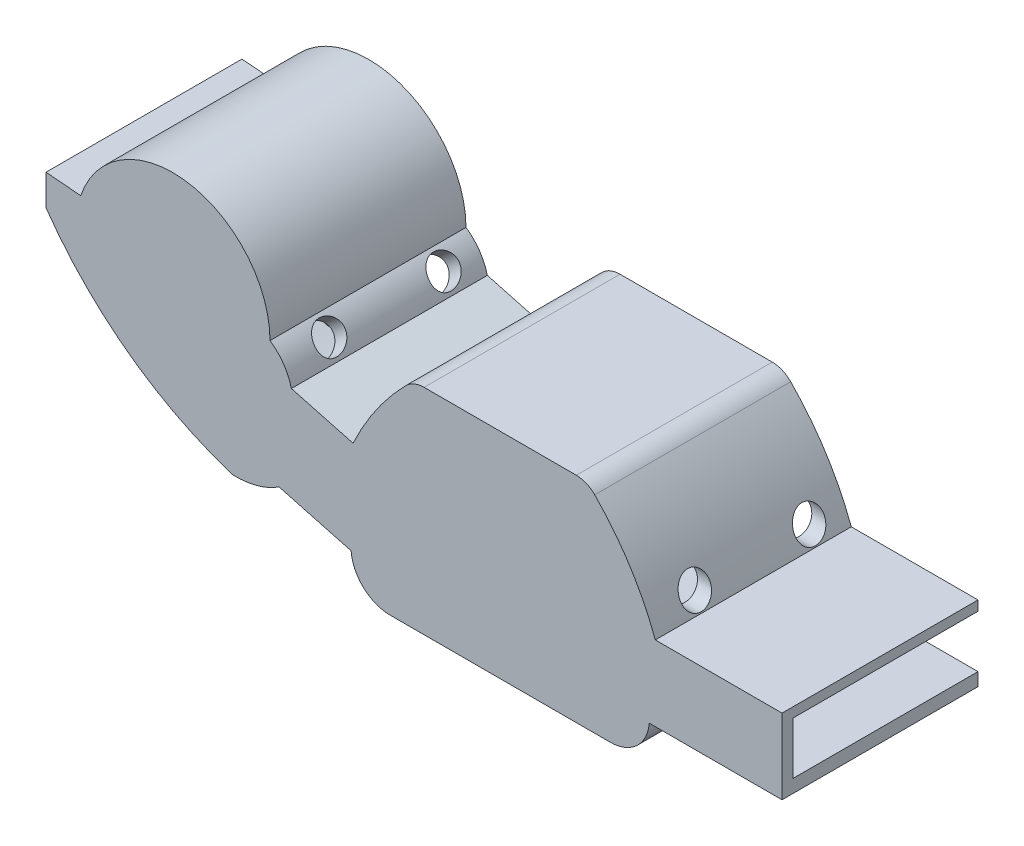
SolidWorks part; units mm, degrees
ref_plane "Front Plane" through (0, 0, 0) normal (0, 0, 1) x (1, 0, 0)
ref_plane "Top Plane" through (0, 0, 0) normal (0, 1, 0) x (1, 0, 0)
ref_plane "Right Plane" through (0, 0, 0) normal (1, 0, 0) x (0, 0, -1)
sketch "Sketch1" plane through (0, 0, 0) normal (0, 0, 1) x (1, 0, 0)
  line L23 (-11.1807, 10.652) -> (-11.4807, 9.152)
  line L24 (-11.4807, 9.152) -> (-11.7807, 10.652)
  line L25 (-11.7807, 10.652) -> (-12.4807, 10.652)
  line L36 (-12.4807, 10.652) -> (-12.7807, 9.152)
  line L40 (-12.7807, 9.152) -> (-13.0807, 10.652)
  line L41 (-13.0807, 10.652) -> (-13.7547, 10.652)
  line L47 (-13.7547, 10.652) -> (-14.0547, 9.152)
  line L48 (-14.0547, 9.152) -> (-14.3547, 10.652)
  line L49 (-14.3547, 10.652) -> (-15.0547, 10.652)
  line L50 (-15.0547, 10.652) -> (-15.3547, 9.152)
  line L51 (-15.3547, 9.152) -> (-15.6547, 10.652)
  line L52 (-15.6547, 10.652) -> (-16.3547, 10.652)
  line L53 (-16.3547, 10.652) -> (-16.6547, 9.152)
  line L54 (-16.6547, 9.152) -> (-16.9547, 10.652)
  line L55 (-16.9547, 10.652) -> (-17.6547, 10.652)
  line L80 (-17.6547, 10.652) -> (-17.9547, 9.152)
  line L171 (8.2817, 1.895) -> (-3.6348, 1.895)
  line L172 (-10.5067, 10.652) -> (-11.1807, 10.652)
  line L173 (-9.9067, 10.652) -> (-9.3532, 10.652)
  line L175 (-46.0443, 15.2577) -> (-46.3443, 16.3976)
  line L176 (-9.9067, 10.652) -> (-10.2067, 9.152)
  line L177 (-10.2067, 9.152) -> (-10.5067, 10.652)
  line L178 (-49.6428, 15.7937) -> (-49.9428, 14.4937)
  line L179 (-3.7183, -2.905) -> (8.2817, -2.905)
  line L180 (-2.7142, -4.105) -> (9.4817, -4.105)
  line L183 (9.4817, 2.795) -> (9.4817, -4.105)
  line L184 (8.2817, 1.895) -> (8.2817, -2.905)
  line L185 (-2.1578, 2.795) -> (9.4817, 2.795)
  line L186 (-54.0874, 6.0654) -> (-57.3849, 10.0091)
  line L188 (-43.4443, 14.6312) -> (-43.7443, 15.8853)
  line L189 (-34.4134, -2.9319) -> (-30.1025, -4.0888)
  line L190 (-58.1264, 9.1857) -> (-58.1264, 12.0173)
  line L195 (-57.3849, 10.0091) -> (-57.3849, 10.7452)
  line L197 (-40.8443, 12.4754) -> (-41.1443, 14.2875)
  line L198 (-47.0455, 16.3874) -> (-47.3455, 15.1968)
  line L199 (-36.8194, 5.1686) -> (-29.0928, 3.095)
  line L200 (-23.1547, 9.152) -> (-23.4579, 10.6577)
  line L202 (-47.3455, 15.1968) -> (-47.6455, 16.3297)
  line L204 (-51.2409, 13.6138) -> (-51.5409, 14.6859)
  line L205 (-55.3415, 9.1857) -> (-56.9992, 10.3046)
  line L206 (-49.9428, 14.4937) -> (-50.2428, 15.5168)
  line L208 (-40.5443, 13.6754) -> (-40.8443, 12.4754)
  line L209 (-57.3849, 10.7452) -> (-56.9992, 10.3046)
  line L210 (-42.1443, 13.7602) -> (-42.4443, 15.2573)
  line L211 (-44.4443, 16.1129) -> (-44.7443, 15.0629)
  line L213 (-39.2443, 11.6575) -> (-39.5443, 9.6575)
  line L214 (-44.7443, 15.0629) -> (-45.0443, 16.2535)
  line L215 (-52.2425, 14.0661) -> (-52.5425, 12.1661)
  line L218 (-45.7443, 16.3577) -> (-46.0443, 15.2577)
  line L219 (-50.9409, 15.1138) -> (-51.2409, 13.6138)
  line L220 (-37.9614, -0.7373) -> (-29.1114, -3.1123)
  line L222 (-39.5443, 9.6575) -> (-39.8443, 12.7549)
  line L223 (-41.8443, 14.8602) -> (-42.1443, 13.7602)
  line L224 (-52.5425, 12.1661) -> (-52.8425, 13.3998)
  line L226 (-58.1264, 12.0173) -> (-54.9379, 11.7458)
  line L229 (-43.1443, 15.6312) -> (-43.4443, 14.6312)
  line L230 (-48.3433, 16.2047) -> (-48.6433, 14.9476)
  line L232 (-29.9206, 4.5597) -> (-35.5859, 6.08)
  line L236 (-48.6433, 14.9476) -> (-48.9433, 16.045)
  line L237 (-34.4134, -2.9319) -> (-36.7107, -2.3154)
  line L238 (-19.2547, 9.152) -> (-19.5547, 10.652)
  line L239 (-17.9547, 9.152) -> (-18.2547, 10.652)
  line L240 (-20.2547, 10.652) -> (-20.5547, 9.152)
  line L241 (-18.2547, 10.652) -> (-18.9547, 10.652)
  line L242 (-18.9547, 10.652) -> (-19.2547, 9.152)
  line L243 (-20.8547, 10.652) -> (-21.5547, 10.652)
  line L244 (-20.5547, 9.152) -> (-20.8547, 10.652)
  line L245 (-19.5547, 10.652) -> (-20.2547, 10.652)
  line L246 (-21.5547, 10.652) -> (-21.8547, 9.152)
  line L247 (-22.1547, 10.652) -> (-22.8547, 10.652)
  line L248 (-22.8547, 10.652) -> (-23.1547, 9.152)
  line L249 (-21.8547, 9.152) -> (-22.1547, 10.652)
  line L253 (-23.3968, 12.2681) -> (-9.4143, 12.2681)
  line L254 (-26.0691, -6.2141) -> (-6.7463, -6.2141)
  line L255 (-6.3025, -7.4141) -> (-26.513, -7.4141)
  arc A66 (-2.7142, -4.105) -> (-6.3025, -7.4141) centre (-6.3025, -3.8141) cw
  arc A67 (-3.7183, -2.905) -> (-6.7463, -6.2141) centre (-6.7023, -3.2144) cw
  arc A69 (-7.343, 8.6822) -> (-9.3532, 10.652) centre (-10.3911, 7.5822) ccw
  arc A70 (-7.343, 8.6822) -> (-3.6348, 1.895) centre (-11.6135, 1.9424) cw
  arc A71 (-2.1578, 2.795) -> (-7.7202, 11.551) centre (-25.381, -5.8132) ccw
  arc A72 (-9.4143, 12.2681) -> (-7.7202, 11.551) centre (-9.4143, 9.9085) cw
  arc A73 (-38.5443, 8.0298) -> (-39.2443, 11.6575) centre (-46.5774, 8.3611) ccw
  arc A75 (-23.3968, 12.2681) -> (-25.0909, 11.551) centre (-23.3968, 9.9085) ccw
  arc A76 (-51.5409, 14.6859) -> (-52.2425, 14.0661) centre (-46.5774, 8.3611) ccw
  arc A77 (-29.1114, -3.1123) -> (-26.0691, -6.2141) centre (-26.1131, -3.2144) ccw
  arc A78 (-58.1264, 9.1857) -> (-41.0218, -3.467) centre (-30.718, 28.3501) ccw
  arc A79 (-42.4443, 15.2573) -> (-43.1443, 15.6312) centre (-46.5774, 8.3611) ccw
  arc A80 (-46.3443, 16.3976) -> (-47.0455, 16.3874) centre (-46.5774, 8.3611) ccw
  arc A81 (-47.6455, 16.3297) -> (-48.3433, 16.2047) centre (-46.5774, 8.3611) ccw
  arc A84 (-54.0874, 6.0654) -> (-41.4637, -2.3822) centre (-33.3409, 23.4122) ccw
  arc A87 (-30.1025, -4.0888) -> (-26.513, -7.4141) centre (-26.513, -3.8141) ccw
  arc A89 (-43.7443, 15.8853) -> (-44.4443, 16.1129) centre (-46.5774, 8.3611) ccw
  arc A90 (-48.9433, 16.045) -> (-49.6428, 15.7937) centre (-46.5774, 8.3611) ccw
  arc A91 (-54.9379, 11.7458) -> (-37.5473, 8.9146) centre (-46.4786, 8.8809) cw
  arc A92 (-39.8443, 12.7549) -> (-40.5443, 13.6754) centre (-46.5774, 8.3611) ccw
  arc A93 (-41.4637, -2.3822) -> (-37.9614, -0.7373) centre (-40.6872, 0.5156) ccw
  arc A94 (-50.2428, 15.5168) -> (-50.9409, 15.1138) centre (-46.5774, 8.3611) ccw
  arc A96 (-24.9838, 9.9746) -> (-25.4681, 8.6822) centre (-23.5017, 8.6822) ccw
  arc A98 (-52.8425, 13.3998) -> (-54.5321, 9.5285) centre (-46.5774, 8.3611) ccw
  arc A100 (-36.8194, 5.1686) -> (-38.5443, 8.0298) centre (-40.8332, 4.6994) ccw
  arc A101 (-23.4579, 10.6577) -> (-24.9838, 9.9746) centre (-23.4814, 8.6645) ccw
  arc A102 (-45.0443, 16.2535) -> (-45.7443, 16.3577) centre (-46.5774, 8.3611) ccw
  arc A104 (-29.9206, 4.5597) -> (-25.0909, 11.551) centre (-7.4301, -5.8132) cw
  arc A106 (-41.1443, 14.2875) -> (-41.8443, 14.8602) centre (-46.5774, 8.3611) ccw
  arc A107 (-36.7107, -2.3154) -> (-41.0218, -3.467) centre (-40.6418, 3.756) cw
  arc A109 (-35.5859, 6.08) -> (-37.5473, 8.9146) centre (-40.294, 4.9182) ccw
  arc A110 (-25.4681, 8.6822) -> (-29.0928, 3.095) centre (-21.1976, 1.9424) ccw
  arc A111 (-54.5321, 9.5285) -> (-55.3415, 9.1857) centre (-48.0159, -6.9857) ccw
  dimension "D14" = 12
  dimension "D18" = 4.8
  dimension "D19" = 6.9
  dimension "D20" = 11.9164
extrude "Walls" add sketch "Sketch1" along normal blind 16 contours L242 region at (-4.3511, -5.93, 0)
sketch "Sketch2" plane through (0, 0, 0) normal (0, 0, -1) x (-1, 0, 0)
  line L10 (35.5859, 6.08) -> (29.9206, 4.5597)
  line L12 (35.5859, 6.08) -> (29.9206, 4.5597)
  line L15 (2.1578, 2.795) -> (-9.4817, 2.795)
  line L17 (2.1578, 2.795) -> (-9.4817, 2.795)
  line L18 (-9.4817, 2.795) -> (-9.4817, -4.105)
  line L37 (-9.4817, 2.795) -> (-9.4817, -4.105)
  line L38 (-9.4817, -4.105) -> (2.7142, -4.105)
  line L39 (-9.4817, -4.105) -> (2.7142, -4.105)
  line L40 (23.3968, 12.2681) -> (9.4143, 12.2681)
  line L42 (23.3968, 12.2681) -> (9.4143, 12.2681)
  line L44 (6.3025, -7.4141) -> (26.513, -7.4141)
  line L47 (6.3025, -7.4141) -> (26.513, -7.4141)
  line L53 (30.1025, -4.0888) -> (36.7107, -2.3154)
  line L54 (30.1025, -4.0888) -> (36.7107, -2.3154)
  line L55 (58.1264, 9.1857) -> (58.1264, 12.0173)
  line L56 (58.1264, 9.1857) -> (58.1264, 12.0173)
  line L57 (58.1264, 12.0173) -> (54.9379, 11.7458)
  line L58 (58.1264, 12.0173) -> (54.9379, 11.7458)
  arc A16 (9.4143, 12.2681) -> (7.7202, 11.551) centre (9.4143, 9.9085) ccw
  arc A17 (9.4143, 12.2681) -> (7.7202, 11.551) centre (9.4143, 9.9085) ccw
  arc A25 (7.7202, 11.551) -> (2.1578, 2.795) centre (25.381, -5.8132) ccw
  arc A26 (7.7202, 11.551) -> (2.1578, 2.795) centre (25.381, -5.8132) ccw
  arc A27 (2.7142, -4.105) -> (6.3025, -7.4141) centre (6.3025, -3.8141) ccw
  arc A28 (2.7142, -4.105) -> (6.3025, -7.4141) centre (6.3025, -3.8141) ccw
  arc A30 (29.9206, 4.5597) -> (25.0909, 11.551) centre (7.4301, -5.8132) ccw
  arc A31 (29.9206, 4.5597) -> (25.0909, 11.551) centre (7.4301, -5.8132) ccw
  arc A32 (25.0909, 11.551) -> (23.3968, 12.2681) centre (23.3968, 9.9085) ccw
  arc A33 (25.0909, 11.551) -> (23.3968, 12.2681) centre (23.3968, 9.9085) ccw
  arc A34 (26.513, -7.4141) -> (30.1025, -4.0888) centre (26.513, -3.8141) ccw
  arc A35 (26.513, -7.4141) -> (30.1025, -4.0888) centre (26.513, -3.8141) ccw
  arc A58 (36.7107, -2.3154) -> (41.0218, -3.467) centre (40.6418, 3.756) ccw
  arc A59 (36.7107, -2.3154) -> (41.0218, -3.467) centre (40.6418, 3.756) ccw
  arc A60 (41.0218, -3.467) -> (58.1264, 9.1857) centre (30.718, 28.3501) ccw
  arc A61 (41.0218, -3.467) -> (58.1264, 9.1857) centre (30.718, 28.3501) ccw
  arc A62 (54.9379, 11.7458) -> (37.5473, 8.9146) centre (46.4786, 8.8809) ccw
  arc A63 (54.9379, 11.7458) -> (37.5473, 8.9146) centre (46.4786, 8.8809) ccw
  arc A64 (37.5473, 8.9146) -> (35.5859, 6.08) centre (40.294, 4.9182) ccw
  arc A65 (37.5473, 8.9146) -> (35.5859, 6.08) centre (40.294, 4.9182) ccw
  dimension "D1" = 0
extrude "Base" add sketch "Sketch2" along normal blind 1
sketch "Sketch3" [suppressed] plane through (0, 0, 0) normal (0, 0, 1) x (1, 0, 0)
  line L4 (-65.1711, 5.3832) -> (-63.3958, 4.9067) construction
  line L5 (-84.8697, 19.5134) -> (-85.1843, 17.3997) construction
  line L6 (-51.77, 3.095) -> (-68.5693, 3.095) construction
  line L7 (-68.5693, 6.2951) -> (-68.5693, 3.095) construction
  line L8 (-51.77, 3.095) -> (-54.6697, 3.095) construction
  line L9 (-68.5693, 6.2951) -> (-65.1711, 5.3832) construction
  line L10 (-56.4697, 3.095) -> (-54.6697, 3.095) construction
  line L11 (-80.595, 9.5224) -> (-82.2789, 9.9743)
  line L12 (-80.595, 9.5224) -> (-76.2959, 8.3687) construction
  line L13 (-91.8537, 12.2226) -> (-90.116, 11.8146)
  line L14 (-82.2789, 9.9743) -> (-90.116, 11.8146) construction
  line L15 (-40.77, 3.095) -> (-37.27, 3.095) construction
  line L16 (-3.6422, 1.595) -> (-7.1422, 1.595) construction
  line L17 (-40.77, 3.095) -> (-3.7183, 3.095) construction
  line L18 (-22.2442, 8.652) -> (-22.2442, 3.095) construction
  line L19 (-22.8547, 10.652) -> (-22.1547, 10.652) construction
  line L20 (-22.2442, 10.652) -> (-22.2442, 8.652) construction
  line L21 (-37.27, 3.095) -> (-34.1769, 3.095) construction
  line L22 (-11.7175, 3.095) -> (-7.1422, 1.595) construction
  arc A1 (-82.2789, 9.9743) -> (-90.116, 11.8146) centre (-86.0365, 11.58) ccw
  arc A2 (-91.8537, 12.2226) -> (-80.595, 9.5224) centre (-86.0443, 11.6231) cw
  arc A3 (-54.6697, 3.095) -> (-65.1711, 5.3832) centre (-60.1697, 3.095) ccw construction
  arc A4 (-84.5208, 19.4536) -> (-85.2208, 19.5578) centre (-86.0539, 11.5612) ccw construction
  arc A5 (-56.4697, 3.095) -> (-63.3958, 4.9067) centre (-60.1697, 3.095) ccw construction
  arc A6 (-3.6422, 1.595) -> (-7.343, 8.6822) centre (-11.6135, 1.9424) ccw construction
  arc A7 (-7.1422, 1.595) -> (-37.27, 3.095) centre (-22.9472, -12.5401) ccw construction
  arc A8 (-11.7175, 3.095) -> (-34.1769, 3.095) centre (-22.9472, -12.5401) ccw construction
  dimension "D1" = 11
  dimension "D2" = 2.137
  dimension "D3" = 7.4
  dimension "D8" = 38.5
  dimension "D4" = 3.5184
  dimension "D5" = 3.5
  dimension "D6" = 3.5
  dimension "D7" = 2
sketch "Sketch4" [suppressed] plane through (0, 0, 16) normal (0, 0, 1) x (1, 0, 0)
  line L7 (-69.5947, 0.3005) -> (-71.4824, -0.3779)
  line L10 (-71.4824, -0.3779) -> (-76.1872, 0.8847)
  line L11 (-76.1872, 0.8847) -> (-77.6773, 2.0433)
  line L12 (-40.77, 3.095) -> (-41.1043, 4.1128)
  line L13 (-41.1043, 4.1128) -> (-49.5364, 4.1128)
  line L16 (-67.7226, 6.3478) -> (-68.9499, 7.6397)
  line L17 (-68.9499, 7.6397) -> (-75.0624, 9.2801)
  line L18 (-75.0624, 9.2801) -> (-76.3177, 7.7352)
  line L19 (-49.5364, 4.1128) -> (-51.77, 3.095)
  line L20 (-40.7743, -2.905) -> (-41.0926, -4.1129)
  line L21 (-41.0926, -4.1129) -> (-49.3636, -4.1129)
  line L22 (-49.3636, -4.1129) -> (-51.8007, -2.905)
  arc A0 (-67.7226, 6.3478) -> (-76.3177, 7.7352) centre (-69.7742, 20.955) cw
  arc A1 (-69.5947, 0.3005) -> (-77.6773, 2.0433) centre (-76.3689, -11.5028) ccw
  arc A2 (-40.7743, -2.905) -> (-51.8007, -2.905) centre (-46.2875, -28.5004) ccw
  arc A3 (-40.77, 3.095) -> (-51.77, 3.095) centre (-46.27, 28.5687) cw
extrude "Joint Width" [suppressed] add sketch "Sketch4" against normal blind 16
ref_plane "SideAnchorPlane" through (0, 0, 2.5) normal (0, 0, 1) x (1, 0, 0)
ref_plane "CentralAnchorPlane" through (0, 0, 13) normal (0, 0, 1) x (1, 0, 0)
sketch "Sketch5" [suppressed] plane through (0, 0, 3) normal (0, 0, 1) x (1, 0, 0)
  line L0 (-76.2959, 8.3687) -> (-68.5693, 6.2951) construction
  line L1 (-76.592, 9.4835) -> (-67.8744, 7.144) construction
  line L2 (-77.4258, 10.7304) -> (-66.9487, 7.9187) construction
  line L3 (-76.592, 9.4835) -> (-88.7757, 4.7797)
  line L4 (-77.4258, 10.7304) -> (-90.1205, 5.8293)
  line L5 (-78.0158, 11.7317) -> (-91.096, 6.6818)
  line L6 (-76.2959, 8.3687) -> (-87.6359, 3.9906)
  line L7 (-78.0158, 11.7317) -> (-77.4258, 10.7304)
  line L9 (-76.592, 9.4835) -> (-76.0479, 8.9395)
  line L10 (-76.0479, 8.9395) -> (-76.2959, 8.3687)
  line L11 (-91.096, 6.6818) -> (-91.096, 6.0024)
  line L12 (-91.096, 6.0024) -> (-90.1205, 5.8293)
  line L13 (-88.7757, 4.7797) -> (-88.5883, 3.9906)
  line L14 (-88.5883, 3.9906) -> (-87.6359, 3.9906)
  arc A0 (-76.2959, 8.3687) -> (-78.0208, 11.2299) centre (-80.3097, 7.8995) ccw construction
  arc A1 (-65.3947, 8.6822) -> (-68.5693, 6.2951) centre (-63.493, 2.8486) ccw construction
  arc A2 (-76.2959, 8.3687) -> (-78.0208, 11.2299) centre (-80.3097, 7.8995) ccw construction
  arc A4 (-93.5639, 9.2655) -> (-80.9402, 0.8179) centre (-72.8174, 26.6123) ccw construction
  arc A5 (-93.5639, 9.2655) -> (-80.9402, 0.8179) centre (-72.8174, 26.6123) ccw construction
  dimension "D1" = 1
  dimension "D2" = 1.5
  dimension "D3" = 1.1466
  dimension "D4" = 1.1466
extrude "Boss-Extrude2" [suppressed] add sketch "Sketch5" along normal blind 1 and the other way blind 1 separate body
sketch "Sketch6" [suppressed] plane through (0, 0, 4) normal (0, 0, 1) x (1, 0, 0)
  line L1 (-87.6359, 3.9906) -> (-76.2959, 8.3687)
  line L4 (-78.0158, 11.7317) -> (-91.096, 6.6818)
  line L5 (-91.096, 6.6818) -> (-91.7792, 6.284)
  line L6 (-91.7792, 6.284) -> (-88.4163, 3.7031)
  line L7 (-88.4163, 3.7031) -> (-87.6359, 3.9906)
  line L8 (-78.0158, 11.7317) -> (-75.9969, 10.8669)
  line L9 (-75.9969, 10.8669) -> (-76.2959, 8.3687)
  arc A0 (-93.5639, 9.2655) -> (-80.9402, 0.8179) centre (-72.8174, 26.6123) ccw construction
extrude "Boss-Extrude4" [suppressed] add sketch "Sketch6" along normal blind 1
sketch "Sketch7" [suppressed] plane through (0, 0, 2) normal (0, 0, -1) x (-1, 0, 0)
  line L0 (87.6359, 3.9906) -> (90.1015, 4.9746)
  line L1 (90.1015, 4.9746) -> (91.096, 6.6818)
  line L2 (91.096, 6.6818) -> (78.0158, 11.7317)
  line L3 (78.0158, 11.7317) -> (76.2959, 10.4542)
  line L4 (76.2959, 10.4542) -> (76.2959, 8.3687)
  line L5 (76.2959, 8.3687) -> (87.6359, 3.9906)
extrude "Boss-Extrude5" [suppressed] add sketch "Sketch7" along normal blind 1
extrude "Boss-Extrude6" [suppressed] add sketch "Sketch3" along normal up to surface (16 mm away)
ref_plane "Plane3" through (-55, 0, 0) normal (1, 0, 0) x (0, 0, -1)
sketch "Sketch14" plane through (-55, 0, 0) normal (1, 0, 0) x (0, 0, -1)
  line L0 (-16, 3.9339) -> (1, 3.9339) construction
  line L1 (1, 2.795) -> (1, 11.551) construction
  line L2 (-16, 9.2861) -> (1, 9.2861) construction
  line L3 (-16, 11.551) -> (-16, 2.795) construction
  line L4 (-7.5, 9.2861) -> (-7.5, 3.9339) construction
  line L6 (-7.5, 6.61) -> (-16, 6.61) construction
  line L7 (-16, 2.795) -> (-16, 3.095) construction
  line L8 (-16, 9.2861) -> (-16, 3.9339) construction
  circle A4 centre (-12.75, 6.61) radius 1.4
  circle A5 centre (-2.25, 6.61) radius 1.4
  circle A6 centre (-7.5, 6.61) radius 1.4 construction
  dimension "D1" = 2.8
  dimension "D2" = 5.25
  dimension "D3" = 0.3
extrude "Cut-Extrude2" cut sketch "Sketch14" along normal up to surface (2.3313 mm away) from offset 25 up to face at (-27.5858, 6.0868, 8)
sketch "Sketch15" plane through (0, 0, 0) normal (1, 0, 0) x (0, 0, -1)
  line L1 (-16, 2.795) -> (1, 2.795) construction
  line L5 (1, 2.795) -> (1, 5.795) construction
  line L6 (1, 2.795) -> (1, 11.551) construction
  line L7 (1, 5.795) -> (-16, 5.795) construction
  line L8 (-7.5, 5.795) -> (-7.5, 2.795) construction
  line L9 (-16, 11.551) -> (-16, 2.795) construction
  line L10 (-7.5, 4.295) -> (-16, 4.295) construction
  circle A4 centre (-12.75, 4.295) radius 1.4
  circle A5 centre (-2.25, 4.295) radius 1.4
  circle A6 centre (-7.5, 4.295) radius 1.4 construction
  dimension "D2" = 5.25
  dimension "D1" = 2.8
extrude "Cut-Extrude3" cut sketch "Sketch15" against normal up to surface (3.9894 mm away) up to face at (-5.0502, 5.5283, 8)
ref_plane "Plane4" through (-17.9029, -15.0104, 0) normal (0.7663, 0.6425, 0) x (0, 0, -1)
sketch "Sketch16" plane through (-17.9029, -15.0104, 0) normal (0.7663, 0.6425, 0) x (0, 0, -1)
  line L0 (-16, 27.5227) -> (1, 27.5227) construction
  line L1 (-2.2201, 32.1448) -> (-13, 32.1448) construction
  line L2 (-13, 55) -> (-13, -55) construction
  line L3 (-16, 30.955) -> (-16, 27.5227) construction
  line L6 (-16, 29.2388) -> (1, 29.2388) construction
  line L7 (-7.61, 32.1448) -> (-13, 32.1448) construction
  line L12 (-16, 30.955) -> (1, 30.955) construction
  line L13 (-7.5, 30.955) -> (-7.5, 27.5227) construction
  circle A0 centre (-2.2201, 32.1448) radius 1.4 construction
  circle A1 centre (-12.86, 32.1448) radius 1.4 construction
  circle A2 centre (-12.75, 29.2388) radius 1.4
  circle A3 centre (-2.25, 29.2388) radius 1.4
  circle A4 centre (-7.5, 29.2388) radius 1.4 construction
  dimension "D1" = 2.8
  dimension "D4" = 5.25
  dimension "D5" = 2.8
  dimension "D3" = 5.25
extrude "Cut-Extrude4" cut sketch "Sketch16" against normal up to surface and the other way up to surface up to face at (-50.0906, 2.1612, 7.5) other way up to face at (-36.4364, 7.5874, 7.5)
ref_plane "Plane5" [suppressed] through (-49.2204, 17.9364, 0) normal (-0.9396, 0.3424, 0) x (0, 0, -1)
sketch "Sketch18" [suppressed] plane through (-49.2204, 17.9364, 0) normal (-0.9396, 0.3424, 0) x (0, 0, -1)
  line L0 (-16, 8.7623) -> (0, 8.7623) construction
  line L1 (-16, 7.8123) -> (-16, 9.3835) construction
  line L2 (-16, 10.9591) -> (-16, 7.8079) construction
  line L3 (-16, 9.3835) -> (1, 9.3835) construction
  line L4 (1, 7.8079) -> (1, 10.9591) construction
  line L5 (-16, 7.8123) -> (1, 7.8123) construction
  line L6 (-7.5, 9.3835) -> (-7.5, 7.8123) construction
  line L14 (-7.5, 9.3835) -> (-16, 9.3835) construction
  circle A2 centre (-12.75, 9.3835) radius 1.4
  circle A3 centre (-2.25, 9.3835) radius 1.4 construction
  circle A4 centre (-7.5, 9.3835) radius 1.4
  dimension "D1" = 2.8
  dimension "D3" = 17
  dimension "D4" = 0.95
extrude "Cut-Extrude5" [suppressed] cut sketch "Sketch18" against normal up to surface (1.3124 mm away)
sketch "Sketch19" plane through (0, 0, 0) normal (0, 0, 1) x (1, 0, 0)
  line L776 (-11.1807, 10.652) -> (-11.4807, 9.152)
  line L777 (-11.4807, 9.152) -> (-11.7807, 10.652)
  line L778 (-11.7807, 10.652) -> (-12.4807, 10.652)
  line L779 (-12.4807, 10.652) -> (-12.7807, 9.152)
  line L780 (-12.7807, 9.152) -> (-13.0807, 10.652)
  line L781 (-13.0807, 10.652) -> (-13.7547, 10.652)
  line L782 (-13.7547, 10.652) -> (-14.0547, 9.152)
  line L783 (-14.0547, 9.152) -> (-14.3547, 10.652)
  line L784 (-14.3547, 10.652) -> (-15.0547, 10.652)
  line L785 (-15.0547, 10.652) -> (-15.3547, 9.152)
  line L786 (-15.3547, 9.152) -> (-15.6547, 10.652)
  line L787 (-15.6547, 10.652) -> (-16.3547, 10.652)
  line L788 (-16.3547, 10.652) -> (-16.6547, 9.152)
  line L789 (-16.6547, 9.152) -> (-16.9547, 10.652)
  line L790 (-16.9547, 10.652) -> (-17.6547, 10.652)
  line L791 (-17.6547, 10.652) -> (-17.9547, 9.152)
  line L792 (8.2817, 1.895) -> (-3.6348, 1.895)
  line L793 (-10.5067, 10.652) -> (-11.1807, 10.652)
  line L794 (-9.9067, 10.652) -> (-9.3532, 10.652)
  line L795 (-46.0443, 15.2577) -> (-46.3443, 16.3976)
  line L796 (-9.9067, 10.652) -> (-10.2067, 9.152)
  line L797 (-10.2067, 9.152) -> (-10.5067, 10.652)
  line L798 (-49.6428, 15.7937) -> (-49.9428, 14.4937)
  line L799 (-3.7183, -2.905) -> (8.2817, -2.905)
  line L802 (8.2817, 1.895) -> (8.2817, -2.905)
  line L804 (-54.0874, 6.0654) -> (-57.3849, 10.0091)
  line L805 (-43.4443, 14.6312) -> (-43.7443, 15.8853)
  line L808 (-57.3849, 10.0091) -> (-57.3849, 10.7452)
  line L809 (-40.8443, 12.4754) -> (-41.1443, 14.2875)
  line L810 (-47.0455, 16.3874) -> (-47.3455, 15.1968)
  line L811 (-36.8194, 5.1686) -> (-29.0928, 3.095)
  line L812 (-23.1547, 9.152) -> (-23.4579, 10.6577)
  line L813 (-47.3455, 15.1968) -> (-47.6455, 16.3297)
  line L814 (-51.2409, 13.6138) -> (-51.5409, 14.6859)
  line L815 (-55.3415, 9.1857) -> (-56.9992, 10.3046)
  line L816 (-49.9428, 14.4937) -> (-50.2428, 15.5168)
  line L817 (-40.5443, 13.6754) -> (-40.8443, 12.4754)
  line L818 (-57.3849, 10.7452) -> (-56.9992, 10.3046)
  line L819 (-42.1443, 13.7602) -> (-42.4443, 15.2573)
  line L820 (-44.4443, 16.1129) -> (-44.7443, 15.0629)
  line L821 (-39.2443, 11.6575) -> (-39.5443, 9.6575)
  line L822 (-44.7443, 15.0629) -> (-45.0443, 16.2535)
  line L823 (-52.2425, 14.0661) -> (-52.5425, 12.1661)
  line L824 (-45.7443, 16.3577) -> (-46.0443, 15.2577)
  line L825 (-50.9409, 15.1138) -> (-51.2409, 13.6138)
  line L826 (-37.9614, -0.7373) -> (-29.1114, -3.1123)
  line L827 (-39.5443, 9.6575) -> (-39.8443, 12.7549)
  line L828 (-41.8443, 14.8602) -> (-42.1443, 13.7602)
  line L829 (-52.5425, 12.1661) -> (-52.8425, 13.3998)
  line L831 (-43.1443, 15.6312) -> (-43.4443, 14.6312)
  line L832 (-48.3433, 16.2047) -> (-48.6433, 14.9476)
  line L834 (-48.6433, 14.9476) -> (-48.9433, 16.045)
  line L836 (-19.2547, 9.152) -> (-19.5547, 10.652)
  line L837 (-17.9547, 9.152) -> (-18.2547, 10.652)
  line L838 (-20.2547, 10.652) -> (-20.5547, 9.152)
  line L839 (-18.2547, 10.652) -> (-18.9547, 10.652)
  line L840 (-18.9547, 10.652) -> (-19.2547, 9.152)
  line L841 (-20.8547, 10.652) -> (-21.5547, 10.652)
  line L842 (-20.5547, 9.152) -> (-20.8547, 10.652)
  line L843 (-19.5547, 10.652) -> (-20.2547, 10.652)
  line L844 (-21.5547, 10.652) -> (-21.8547, 9.152)
  line L845 (-22.1547, 10.652) -> (-22.8547, 10.652)
  line L846 (-22.8547, 10.652) -> (-23.1547, 9.152)
  line L847 (-21.8547, 9.152) -> (-22.1547, 10.652)
  line L849 (-26.0691, -6.2141) -> (-6.7463, -6.2141)
  arc A296 (-3.7183, -2.905) -> (-6.7463, -6.2141) centre (-6.7023, -3.2144) cw
  arc A297 (-7.343, 8.6822) -> (-9.3532, 10.652) centre (-10.3911, 7.5822) ccw
  arc A298 (-7.343, 8.6822) -> (-3.6348, 1.895) centre (-11.6135, 1.9424) cw
  arc A301 (-38.5443, 8.0298) -> (-39.2443, 11.6575) centre (-46.5774, 8.3611) ccw
  arc A303 (-51.5409, 14.6859) -> (-52.2425, 14.0661) centre (-46.5774, 8.3611) ccw
  arc A304 (-29.1114, -3.1123) -> (-26.0691, -6.2141) centre (-26.1131, -3.2144) ccw
  arc A306 (-42.4443, 15.2573) -> (-43.1443, 15.6312) centre (-46.5774, 8.3611) ccw
  arc A307 (-46.3443, 16.3976) -> (-47.0455, 16.3874) centre (-46.5774, 8.3611) ccw
  arc A308 (-47.6455, 16.3297) -> (-48.3433, 16.2047) centre (-46.5774, 8.3611) ccw
  arc A309 (-54.0874, 6.0654) -> (-41.4637, -2.3822) centre (-33.3409, 23.4122) ccw
  arc A311 (-43.7443, 15.8853) -> (-44.4443, 16.1129) centre (-46.5774, 8.3611) ccw
  arc A312 (-48.9433, 16.045) -> (-49.6428, 15.7937) centre (-46.5774, 8.3611) ccw
  arc A314 (-39.8443, 12.7549) -> (-40.5443, 13.6754) centre (-46.5774, 8.3611) ccw
  arc A315 (-41.4637, -2.3822) -> (-37.9614, -0.7373) centre (-40.6872, 0.5156) ccw
  arc A316 (-50.2428, 15.5168) -> (-50.9409, 15.1138) centre (-46.5774, 8.3611) ccw
  arc A317 (-24.9838, 9.9746) -> (-25.4681, 8.6822) centre (-23.5017, 8.6822) ccw
  arc A318 (-52.8425, 13.3998) -> (-54.5321, 9.5285) centre (-46.5774, 8.3611) ccw
  arc A319 (-36.8194, 5.1686) -> (-38.5443, 8.0298) centre (-40.8332, 4.6994) ccw
  arc A320 (-23.4579, 10.6577) -> (-24.9838, 9.9746) centre (-23.4814, 8.6645) ccw
  arc A321 (-45.0443, 16.2535) -> (-45.7443, 16.3577) centre (-46.5774, 8.3611) ccw
  arc A323 (-41.1443, 14.2875) -> (-41.8443, 14.8602) centre (-46.5774, 8.3611) ccw
  arc A326 (-25.4681, 8.6822) -> (-29.0928, 3.095) centre (-21.1976, 1.9424) ccw
  arc A327 (-54.5321, 9.5285) -> (-55.3415, 9.1857) centre (-48.0159, -6.9857) ccw
  dimension "D2" = 4.8
  dimension "D6" = 12
  dimension "D7" = 11.9164
extrude "Cut-Extrude6" cut sketch "Sketch19" against normal up to surface (1 mm away) up to face at (-24.5133, 4.1091, -1)
sketch "Sketch20" plane through (0, 0, 0) normal (0, 0, 1) x (1, 0, 0)
  line L0 (-54.4035, 2.7093) -> (-51.9246, 5.1264)
  line L1 (-51.5903, 4.754) -> (-54.0545, 2.3513)
  line L2 (-51.9246, 5.1264) -> (-51.5903, 4.754)
  line L3 (-54.0545, 2.3513) -> (-54.4035, 2.7093)
  line L5 (-42.683, -1.1188) -> (-43.7146, -3.8542)
  line L9 (-43.7146, -3.8542) -> (-43.2468, -4.0306)
  line L10 (-16.6675, -3.3719) -> (-16.1675, -3.3719)
  line L11 (-16.6675, -3.3719) -> (-16.6675, -9.3408)
  line L12 (-16.6675, -9.3408) -> (-16.1675, -9.3408)
  line L13 (-16.1675, -3.3719) -> (-16.1675, -9.3408)
  line L14 (-43.2468, -4.0306) -> (-42.2152, -1.2952)
  line L15 (-42.2152, -1.2952) -> (-42.683, -1.1188)
  line L17 (-56.6084, 9.9069) -> (-40.6872, -2.4844) construction
  dimension "D1" = 0.5
  dimension "D2" = 0.5
  dimension "D4" = 0.5
extrude "Cut-Extrude7" cut sketch "Sketch20" along normal blind 13 from offset 1
sketch "Sketch21" plane through (0, 0, 0) normal (0, 0, 1) x (1, 0, 0)
  line L0 (9.4817, 2.795) -> (9.4817, -4.105) construction
  line L3 (8.2817, -2.905) -> (9.4817, -2.905)
  line L4 (9.4817, 1.895) -> (9.4817, -2.905)
  line L5 (8.2817, -2.905) -> (8.2817, 1.895)
  line L6 (8.2817, 1.895) -> (9.4817, 1.895)
  dimension "D1" = 4.8
extrude "Cut-Extrude8" cut sketch "Sketch21" against normal up to surface and the other way up to surface up to face at (-30.7783, 10.31, -1) other way up to face at (-30.7783, 10.31, 16)
ref_plane "Plane6" through (0, 0, 16) normal (0, 0, 1) x (1, 0, 0)
sketch "Sketch22" plane through (0, 0, 16) normal (0, 0, 1) x (1, 0, 0)
  line L381 (-2.7142, -4.105) -> (9.4817, -4.105)
  line L382 (9.4817, 2.795) -> (9.4817, -4.105)
  line L384 (-2.1578, 2.795) -> (9.4817, 2.795)
  line L387 (-34.4134, -2.9319) -> (-30.1025, -4.0888)
  line L388 (-58.1264, 9.1857) -> (-58.1264, 12.0173)
  line L411 (-58.1264, 12.0173) -> (-54.9379, 11.7458)
  line L414 (-29.9206, 4.5597) -> (-35.5859, 6.08)
  line L416 (-34.4134, -2.9319) -> (-36.7107, -2.3154)
  line L429 (-23.3968, 12.2681) -> (-9.4143, 12.2681)
  line L431 (-6.3025, -7.4141) -> (-26.513, -7.4141)
  arc A163 (-2.7142, -4.105) -> (-6.3025, -7.4141) centre (-6.3025, -3.8141) cw
  arc A167 (-2.1578, 2.795) -> (-7.7202, 11.551) centre (-25.381, -5.8132) ccw
  arc A168 (-9.4143, 12.2681) -> (-7.7202, 11.551) centre (-9.4143, 9.9085) cw
  arc A170 (-23.3968, 12.2681) -> (-25.0909, 11.551) centre (-23.3968, 9.9085) ccw
  arc A173 (-58.1264, 9.1857) -> (-41.0218, -3.467) centre (-30.718, 28.3501) ccw
  arc A178 (-30.1025, -4.0888) -> (-26.513, -7.4141) centre (-26.513, -3.8141) ccw
  arc A181 (-54.9379, 11.7458) -> (-37.5473, 8.9146) centre (-46.4786, 8.8809) cw
  arc A190 (-29.9206, 4.5597) -> (-25.0909, 11.551) centre (-7.4301, -5.8132) cw
  arc A192 (-36.7107, -2.3154) -> (-41.0218, -3.467) centre (-40.6418, 3.756) cw
  arc A193 (-35.5859, 6.08) -> (-37.5473, 8.9146) centre (-40.294, 4.9182) ccw
  dimension "D3" = 6.9
extrude "Boss-Extrude7" add sketch "Sketch22" along normal blind 1
